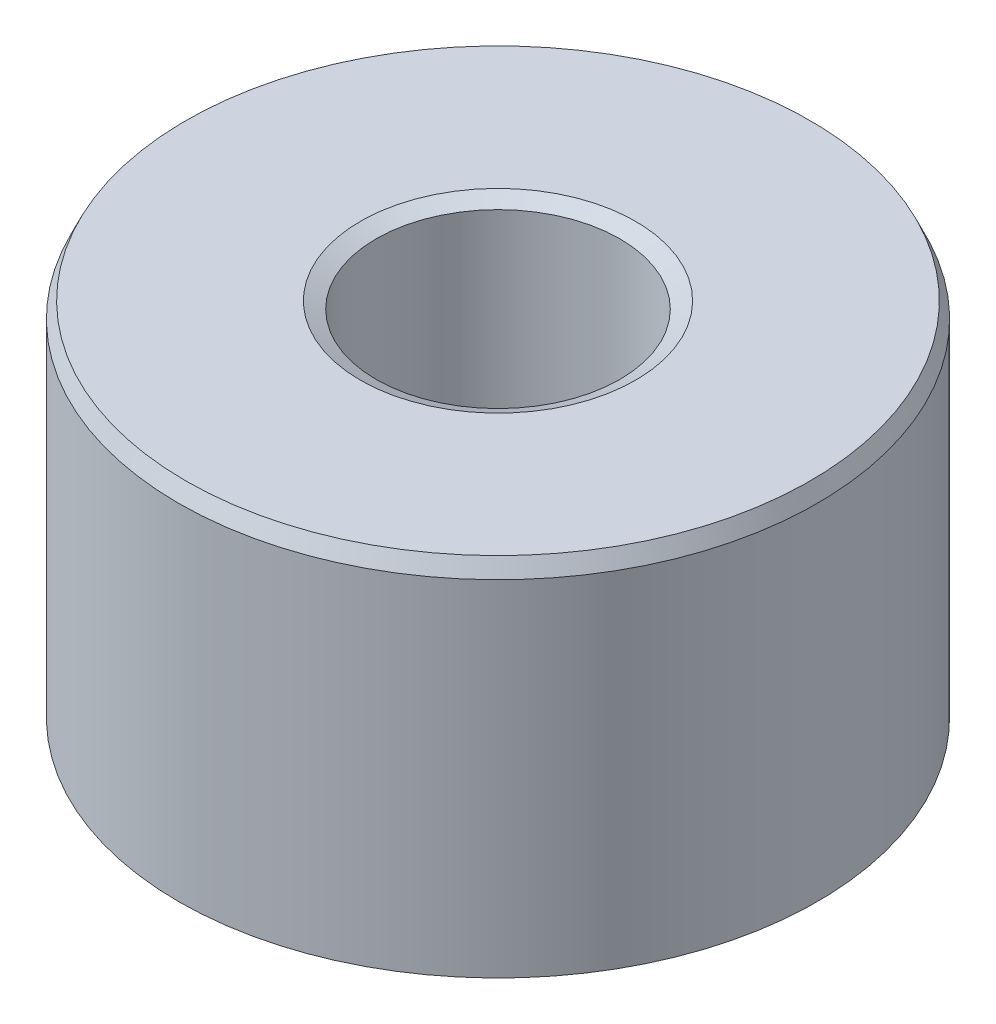
SolidWorks part; units mm, degrees
ref_plane "Front Plane" through (0, 0, 0) normal (0, 0, 1) x (1, 0, 0)
ref_plane "Top Plane" through (0, 0, 0) normal (0, 1, 0) x (1, 0, 0)
ref_plane "Right Plane" through (0, 0, 0) normal (1, 0, 0) x (0, 0, -1)
sketch "Sketch1" plane through (0, 0, 0) normal (0, 1, 0) x (1, 0, 0)
  circle A0 centre (0, 0) radius 10
  dimension "SLEEVE_OD" = 20
extrude "Boss-Extrude1" add sketch "Sketch1" along normal blind 11.5217
sketch "Sketch2" plane through (0, 0, 0) normal (0, 1, 0) x (1, 0, 0)
  circle A0 centre (0, 0) radius 3.8156
  dimension "BORE_D" = 7.6312
extrude "Cut-Extrude1" cut sketch "Sketch2" along normal through all
chamfer "Chamfer1" distance 0.4941 angle 24.593 4 edges at (0, 11.5217, 3.8156) (0, 0, 3.8156) (0, 0, 10) (0, 11.5217, 10) first distance on face at (0, 11.5217, 3.8156) first distance on face at (0, 0, 3.8156) first distance on face at (0, 11.5217, 10)
